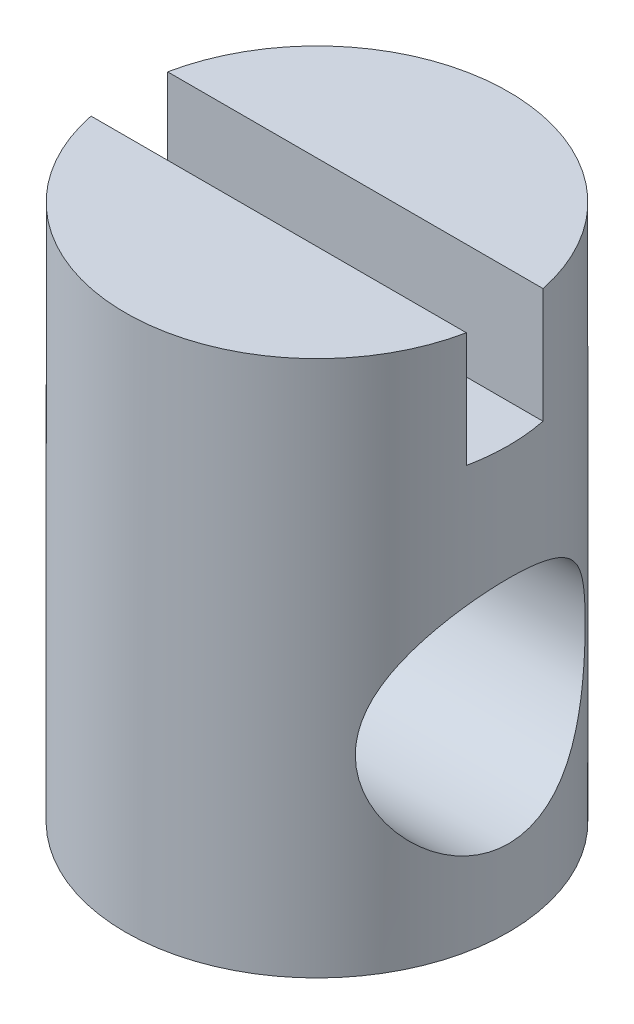
SolidWorks part; units mm, degrees
ref_plane "정면" through (0, 0, 0) normal (0, 0, 1) x (1, 0, 0)
ref_plane "윗면" through (0, 0, 0) normal (0, 1, 0) x (1, 0, 0)
ref_plane "우측면" through (0, 0, 0) normal (1, 0, 0) x (0, 0, -1)
sketch "스케치1" plane through (0, 0, 0) normal (0, 1, 0) x (1, 0, 0)
  circle A0 centre (0, 0) radius 5
  dimension "D1" = 10
extrude "보스-돌출1" add sketch "스케치1" along normal blind 14
sketch "스케치2" plane through (0, 14, 0) normal (0, 1, 0) x (1, 0, 0)
  line L1 (-6.9984, -1) -> (6.9984, -1)
  line L2 (-6.9984, -1) -> (-6.9984, 1)
  line L3 (-6.9984, 1) -> (6.9984, 1)
  line L4 (6.9984, -1) -> (6.9984, 1)
  line L5 (-6.9984, -1) -> (6.9984, 1) construction
  line L6 (-6.9984, 1) -> (6.9984, -1) construction
  point P0 (0, 0)
  dimension "D1" = 2
extrude "컷-돌출1" cut sketch "스케치2" against normal blind 3
sketch "스케치3" plane through (0, 0, 0) normal (1, 0, 0) x (0, 0, -1)
  line L0 (0, 0) -> (0, 5) construction
  circle A0 centre (0, 5) radius 3
  dimension "D1" = 6
  dimension "D2" = 5
extrude "컷-돌출2" cut sketch "스케치3" against normal blind 13 and the other way blind 13
